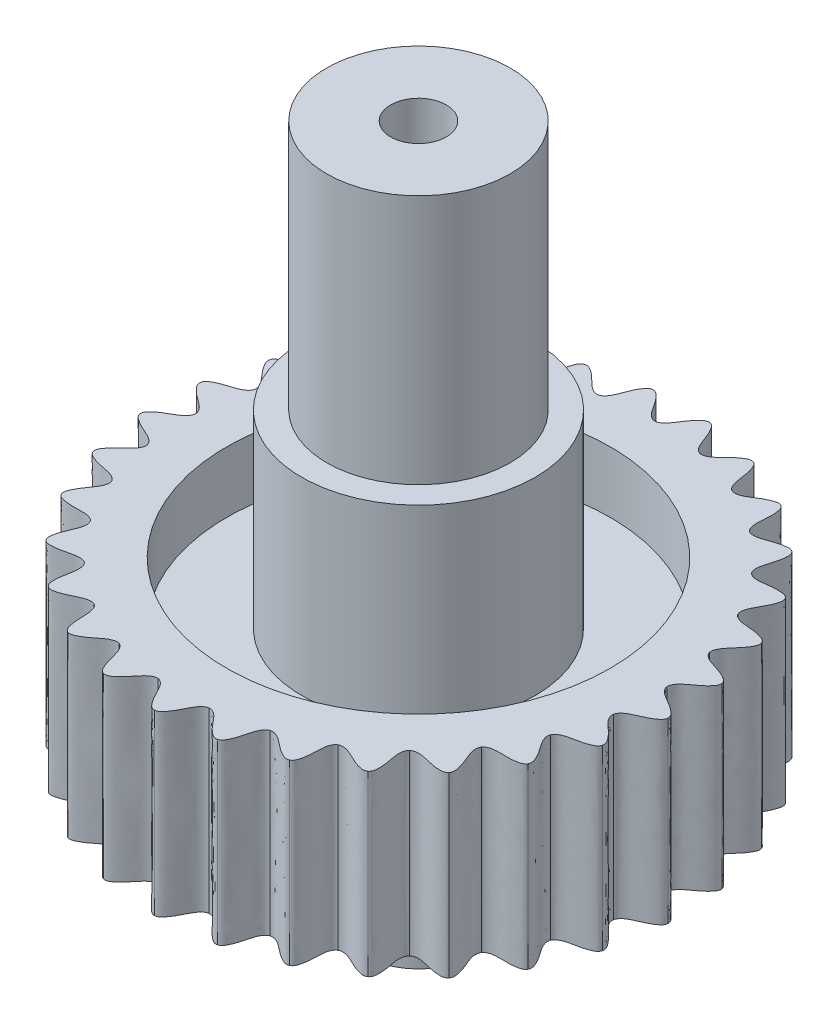
SolidWorks part; units mm, degrees
ref_plane "Front Plane" through (0, 0, 0) normal (0, 0, 1) x (1, 0, 0)
ref_plane "Top Plane" through (0, 0, 0) normal (0, 1, 0) x (1, 0, 0)
ref_plane "Right Plane" through (0, 0, 0) normal (1, 0, 0) x (0, 0, -1)
sketch "Sketch1" plane through (0, 0, 0) normal (0, 0, 1) x (1, 0, 0)
  line L0 (-9.5, 0) -> (-9.5, 6.4)
  line L1 (-9.5, 6.4) -> (-6.9, 6.4)
  line L2 (-6.9, 6.4) -> (-6.9, 4.2)
  line L3 (-6.9, 4.2) -> (-4.2, 4.2)
  line L4 (-4.2, 4.2) -> (-4.2, 11)
  line L5 (-4.2, 11) -> (-3.3, 11)
  line L6 (-3.3, 11) -> (-3.3, 20)
  line L7 (-3.3, 20) -> (0, 20)
  line L8 (-9.5, 0) -> (-6.9, 0)
  line L9 (-6.9, 0) -> (-6.9, 2.7)
  line L10 (-6.9, 2.7) -> (-3.25, 2.7)
  line L11 (-3.25, 2.7) -> (-3.25, -2)
  line L12 (-3.25, -2) -> (0, -2)
  line L13 (0, -2) -> (0, 20) construction
  line L14 (0, 20) -> (0, -2)
  dimension "D1" = 9.5
  dimension "D2" = 3.3
  dimension "D3" = 4.2
  dimension "D4" = 2.6
  dimension "D5" = 3.25
  dimension "D6" = 2.7
  dimension "D7" = 2.2
  dimension "D8" = 6.4
  dimension "D9" = 11
  dimension "D10" = 20
  dimension "D11" = 2
revolve "Revolve1" add sketch "Sketch1" angle 360 about L13
sketch "Sketch2" plane through (0, -2, 0) normal (0, -1, 0) x (1, 0, 0)
  circle A0 centre (0, 0) radius 1
  dimension "D1" = 2
extrude "Cut-Extrude1" cut sketch "Sketch2" against normal through all
sketch "Sketch3" plane through (0, -2, 0) normal (0, -1, 0) x (1, 0, 0)
  line L0 (0, 0) -> (-0.866, -0.5) construction
  line L1 (-0.866, -0.5) -> (-1.7321, -1)
  line L2 (0, 0) -> (0, -2.0439) construction
  line L3 (0, 0) -> (0.866, -0.5) construction
  line L4 (0.866, -0.5) -> (1.7321, -1)
  arc A0 (-0.866, -0.5) -> (0.866, -0.5) centre (0, 0) cw
  circle A1 centre (0, 0) radius 1 construction
  arc A2 (-1.7321, -1) -> (1.7321, -1) centre (0, 0) cw
  dimension "D1" = 60
  dimension "D2" = 1
extrude "Boss-Extrude1" add sketch "Sketch3" along normal blind 3
sketch "Sketch5" plane through (0, 0, 0) normal (0, -1, 0) x (1, 0, 0)
  circle A0 centre (0, 0) radius 9 construction
  dimension "D1" = 18
sketch "Sketch4" plane through (0, 0, 0) normal (0, -1, 0) x (1, 0, 0)
  line L0 (0, 0) -> (0, 9.5) construction
  line L1 (0, 0) -> (2.0422, 9.2779) construction
  line L2 (0, 0) -> (1.0271, 9.4443) construction
  circle A0 centre (0, 0) radius 8.5 construction
  circle A1 centre (0, 0) radius 9.5 construction
  arc A3 (0, 9.5) -> (2.0422, 9.2779) centre (0, 0) cw
  circle A4 centre (0, 0) radius 9 construction
  spline S0 degree 3 poles (0, 9.5) (0.1091, 9.5) (0.289, 9.3046) (0.4909, 8.9624) (0.6431, 8.5935) (0.8504, 8.4576) (0.919, 8.4502) knots 0 0 0 0 0.209177 0.494424 0.866885 1 1 1 1
  spline S1 degree 3 poles (2.0422, 9.2779) (1.9357, 9.3014) (1.7179, 9.1492) (1.4472, 8.8584) (1.2193, 8.5308) (0.9876, 8.4427) (0.919, 8.4502) knots 0 0 0 0 0.209177 0.494424 0.866885 1 1 1 1
  dimension "D2" = 17
  dimension "D1" = 12.414
extrude "Cut-Extrude2" cut sketch "Sketch4" against normal through all
ref_axis "Axis1" through (0, 20, 0) along (0, -1, 0)
pattern_circular "CirPattern1" count 29 over 360 about axis through (0, 20, 0) along (0, -1, 0) of "Cut-Extrude2"
